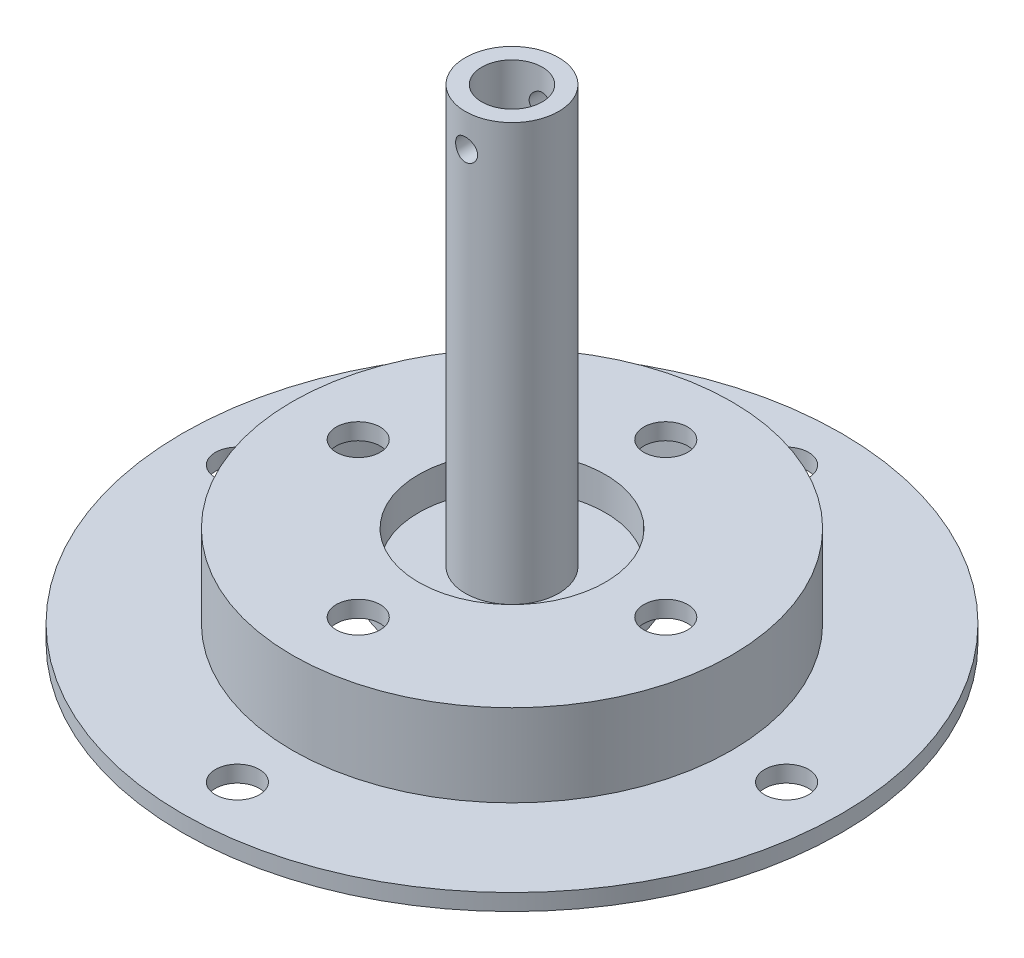
SolidWorks part; units mm, degrees
ref_plane "前视基准面" through (0, 0, 0) normal (0, 0, 1) x (1, 0, 0)
ref_plane "上视基准面" through (0, 0, 0) normal (0, 1, 0) x (1, 0, 0)
ref_plane "右视基准面" through (0, 0, 0) normal (1, 0, 0) x (0, 0, -1)
sketch "草图1" plane through (0, 0, 0) normal (0, 1, 0) x (1, 0, 0)
  circle A0 centre (0, 0) radius 10
  circle A1 centre (0, 0) radius 2.75
  dimension "D1" = 5.5
  dimension "D2" = 20
extrude "凸台-拉伸1" add sketch "草图1" along normal blind 1.5
sketch "草图2" plane through (0, 1.5, 0) normal (0, 1, 0) x (1, 0, 0)
  circle A0 centre (0, 0) radius 8.5
  circle A1 centre (0, 0) radius 10 construction
  circle A2 centre (0, 0) radius 10
  dimension "D1" = 1.5
extrude "凸台-拉伸2" add sketch "草图2" along normal blind 3
sketch "草图3" plane through (0, 1.5, 0) normal (0, 1, 0) x (1, 0, 0)
  circle A0 centre (0, 0) radius 4.25
  circle A1 centre (0, 0) radius 2.75 construction
  circle A2 centre (0, 0) radius 2.75
  dimension "D1" = 8.5
extrude "凸台-拉伸3" add sketch "草图3" along normal blind 38
sketch "草图4" plane through (0, 4.5, 0) normal (0, 1, 0) x (1, 0, 0)
  circle A0 centre (0, 0) radius 8.5 construction
  circle A1 centre (0, 0) radius 8.5
  circle A2 centre (0, 0) radius 20
  circle A3 centre (0, 0) radius 14 construction
  circle A4 centre (0, -14) radius 2
  circle A5 centre (-14, 0) radius 2
  circle A6 centre (14, 0) radius 2
  circle A7 centre (0, 14) radius 2
  dimension "D1" = 40
  dimension "D2" = 28
  dimension "D3" = 4
  dimension "D4" = 4
  dimension "D5" = 4
  dimension "D6" = 4
extrude "凸台-拉伸4" add sketch "草图4" against normal blind 1.5
sketch "草图5" plane through (0, 3, 0) normal (0, -1, 0) x (1, 0, 0)
  circle A0 centre (0, 0) radius 18.5
  circle A1 centre (0, 0) radius 20 construction
  circle A2 centre (0, 0) radius 20
  dimension "D1" = 1.5
extrude "凸台-拉伸5" add sketch "草图5" along normal blind 6
sketch "草图7" plane through (0, 0, 0) normal (0, 0, 1) x (1, 0, 0)
  line L0 (2.75, 39.5) -> (-2.75, 39.5) construction
  circle A0 centre (0, 36.5) radius 1
  dimension "D1" = 2
  dimension "D2" = 3
extrude "切除-拉伸2" cut sketch "草图7" against normal up to next and the other way up to next
sketch "草图8" plane through (0, -3, 0) normal (0, -1, 0) x (1, 0, 0)
  circle A0 centre (0, 0) radius 30
  circle A1 centre (0, 0) radius 18.5 construction
  circle A2 centre (0, 0) radius 18.5
  circle A3 centre (0, 0) radius 25 construction
  circle A4 centre (25, 0) radius 2
  circle A5 centre (-25, 0) radius 2
  circle A6 centre (0, -25) radius 2
  circle A7 centre (0, 25) radius 2
  dimension "D1" = 60
  dimension "D2" = 50
  dimension "D3" = 4
  dimension "D4" = 4
  dimension "D5" = 4
  dimension "D6" = 4
extrude "凸台-拉伸6" add sketch "草图8" along normal blind 1.5
